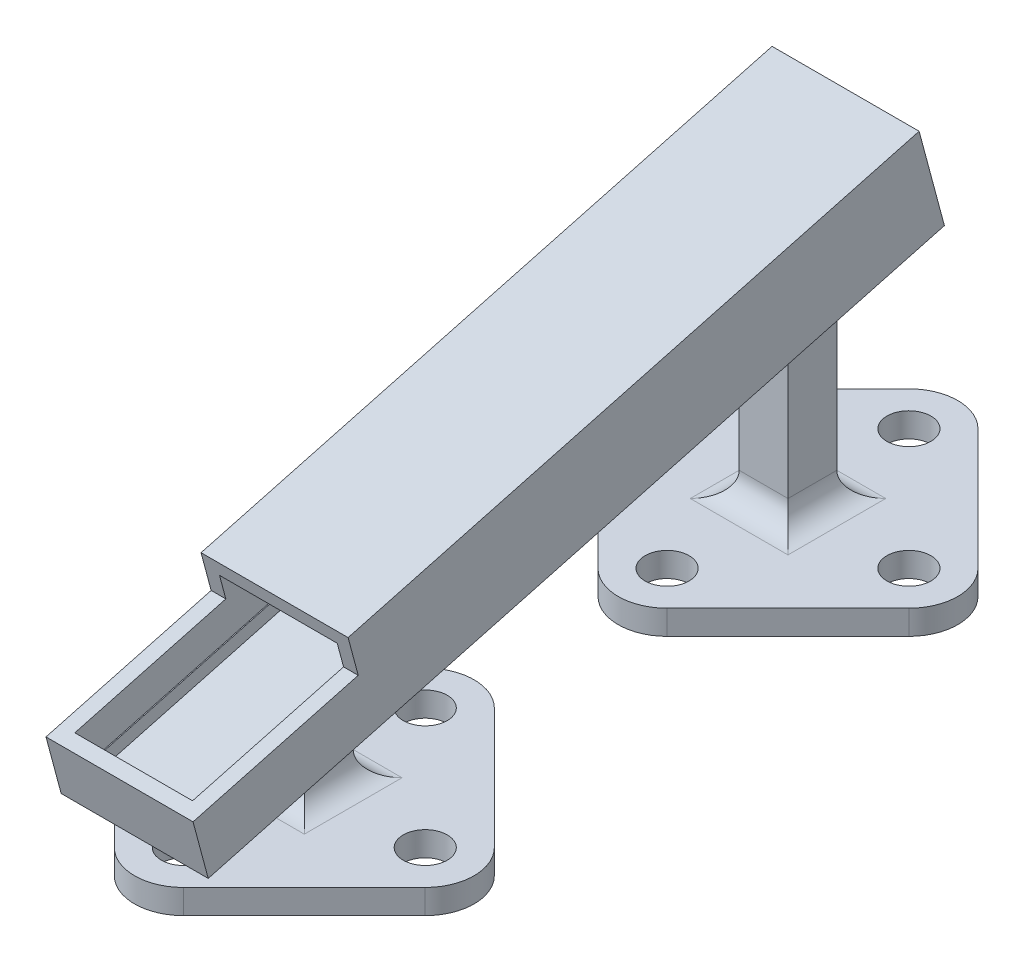
SolidWorks part; units mm, degrees
ref_plane "Front" through (0, 0, 0) normal (0, 0, 1) x (1, 0, 0)
ref_plane "Top" through (0, 0, 0) normal (0, 1, 0) x (1, 0, 0)
ref_plane "Right" through (0, 0, 0) normal (1, 0, 0) x (0, 0, -1)
ref_axis "Axis1" through (0, 55, 0) along (0, -1, 0)
ref_axis "Axis2" through (88.99, 0, 0) along (-1, 0, 0)
ref_axis "Axis3" through (0, 0, 55) along (0, 0, -1)
sketch "Sketch1" plane through (0, 0, 0) normal (0, 1, 0) x (1, 0, 0)
  line L0 (-24.75, 0) -> (0, 24.75) construction
  line L9 (-24.75, 0) -> (0, -24.75) construction
  line L11 (0, 24.75) -> (24.75, 0) construction
  line L12 (0, -24.75) -> (24.75, 0) construction
  line L13 (-24.75, 0) -> (24.75, 0) construction
  line L14 (0, 24.75) -> (0, -24.75) construction
  line L15 (-31.8211, 7.0711) -> (-7.0711, 31.8211)
  line L16 (7.0711, 31.8211) -> (31.8211, 7.0711)
  line L17 (7.0711, -31.8211) -> (31.8211, -7.0711)
  line L18 (-31.8211, -7.0711) -> (-7.0711, -31.8211)
  line L19 (0, -38.8921) -> (38.8921, 0) construction
  line L20 (-38.8921, 0) -> (0, -38.8921) construction
  line L21 (0, 38.8921) -> (38.8921, 0) construction
  line L22 (-38.8921, 0) -> (0, 38.8921) construction
  arc A4 (7.0711, -31.8211) -> (-7.0711, -31.8211) centre (0, -24.75) cw
  arc A5 (31.8211, 7.0711) -> (31.8211, -7.0711) centre (24.75, 0) cw
  arc A6 (-7.0711, 31.8211) -> (7.0711, 31.8211) centre (0, 24.75) cw
  arc A7 (-31.8211, 7.0711) -> (-31.8211, -7.0711) centre (-24.75, 0) ccw
  circle A8 centre (0, 24.75) radius 4.5
  circle A9 centre (24.75, 0) radius 4.5
  circle A10 centre (0, -24.75) radius 4.5
  circle A11 centre (-24.75, 0) radius 4.5
  point P1 (0, 0)
  dimension "D3" = 10
  dimension "D4" = 9
  dimension "D1" = 49.5
  dimension "D2" = 10
extrude "Boss-Extrude1" add sketch "Sketch1" along normal mid plane 5
ref_plane "Plane1" through (0, 0, 49.5) normal (0, 0, 1) x (1, 0, 0)
mirror "Mirror3" about plane through (0, 0, 49.5) normal (0, 0, 1) of bodies 101
sketch "Sketch2" plane through (0, 0, 0) normal (1, 0, 0) x (0, 0, -1)
  line L0 (-106.0711, 2.5) -> (-130.8211, 2.5) construction
  line L1 (-104, 2.5) -> (-94, 2.5)
  line L2 (-104, 2.5) -> (-104, 47.5)
  line L3 (-104, 47.5) -> (-94, 47.5)
  line L4 (-94, 2.5) -> (-94, 47.5)
  line L5 (-106.0711, -2.5) -> (-91.9289, -2.5) construction
  line L6 (-67.1789, -2.5) -> (-91.9289, -2.5) construction
  point P8 (-99, -2.5)
  point P9 (-99, 47.5)
  dimension "D1" = 10
  dimension "D2" = 50
extrude "Boss-Extrude2" add sketch "Sketch2" along normal mid plane 10 separate body
mirror "Mirror5" about plane through (0, 0, 49.5) normal (0, 0, 1) of bodies 103
sketch "Sketch3" plane through (0, 0, 0) normal (1, 0, 0) x (0, 0, -1)
  line L0 (-104, 17.5) -> (5, 46.7065)
  line L1 (-67.1789, -2.5) -> (-91.9289, -2.5) construction
  line L2 (-104, 47.5) -> (-104, 2.5) construction
  line L3 (-106.0711, 2.5) -> (-130.8211, 2.5) construction
  line L4 (5, 47.5) -> (5, 2.5) construction
  point P6 (-104, 17.5)
  dimension "D1" = 15
  dimension "D2" = 15
extrude "Cut-Extrude1" cut sketch "Sketch3" against normal through all both and the other way through all
sketch "Sketch4" plane through (0, 0, 0) normal (1, 0, 0) x (0, 0, -1)
  line L0 (-130.8211, 10.3133) -> (14.0678, 49.1362)
  line L1 (-130.8211, 10.3133) -> (-131.3387, 12.2452)
  line L2 (14.0678, 49.1362) -> (13.5502, 51.068)
  line L3 (-131.3387, 12.2452) -> (13.5502, 51.068)
  line L6 (-104, 17.5) -> (-94, 20.1795) construction
  dimension "D1" = 2
  dimension "D2" = 150
extrude "Boss-Extrude3" add sketch "Sketch4" along normal mid plane 24.1 separate body
combine bodies "Combine1" operation type add bodies to combine 102 106
combine bodies "Combine2" operation type add bodies to combine 107 101
fillet "Fillet1" radius 5 4 edges at (0, 2.5, 94) (-5, 2.5, 99) (0, 2.5, 104) (5, 2.5, 99)
fillet "Fillet2" radius 5 4 edges at (0, 2.5, 5) (0, 2.5, -5) (-5, 2.5, 0) (5, 2.5, 0)
sketch "Sketch5" plane through (0, 44.2596, 11.8593) normal (0, 0.9659, 0.2588) x (1, 0, 0)
  line L0 (12.05, -111.6442) -> (0, -111.6442) construction
  line L1 (12.05, 26.3058) -> (12.05, -123.6942) construction
  line L2 (0, -111.6442) -> (0, -123.6942) construction
  line L3 (12.05, -123.6942) -> (-12.05, -123.6942) construction
  line L4 (-11.83, -111.6442) -> (-12.05, -123.6942)
  line L5 (-12.05, -123.6942) -> (0, -123.6942)
  line L6 (0, -123.6942) -> (12.05, -123.6942)
  line L7 (12.05, -123.6942) -> (12.05, -111.6442)
  circle A0 centre (0, -111.6442) radius 8.73 construction
  circle A1 centre (0, -111.6442) radius 8.83
  circle A2 centre (0, -111.6442) radius 11.83
  dimension "D1" = 17.46
  dimension "D2" = 0.1
  dimension "D3" = 3
sketch "Sketch6" plane through (0, 44.2596, 11.8593) normal (0, 0.9659, 0.2588) x (1, 0, 0)
  line L4 (-12.05, 26.3058) -> (-12.05, -123.6942)
  line L5 (-12.05, -123.6942) -> (12.05, -123.6942)
  line L6 (12.05, -123.6942) -> (12.05, 26.3058)
  line L7 (12.05, 26.3058) -> (-12.05, 26.3058)
  line L8 (-12.05, 26.3058) -> (-12.05, -123.6942)
  line L9 (-12.05, -123.6942) -> (12.05, -123.6942)
  line L10 (12.05, -123.6942) -> (12.05, 26.3058)
  line L11 (12.05, 26.3058) -> (-12.05, 26.3058)
  line L16 (-15.05, 29.3058) -> (-15.05, -126.6942)
  line L17 (-15.05, -126.6942) -> (15.05, -126.6942)
  line L18 (15.05, -126.6942) -> (15.05, 29.3058)
  line L19 (15.05, 29.3058) -> (-15.05, 29.3058)
  line L20 (-15.05, 29.3058) -> (-15.05, -126.6942)
  line L21 (-15.05, -126.6942) -> (15.05, -126.6942)
  line L22 (15.05, -126.6942) -> (15.05, 29.3058)
  line L23 (15.05, 29.3058) -> (-15.05, 29.3058)
  dimension "D1" = 0
  dimension "D2" = 3
extrude "Boss-Extrude4" add sketch "Sketch6" against normal up to vertex (2 mm away) and the other way blind 10 up to point (12.05, 49.1362, -14.0678)
sketch "Sketch7" plane through (0, 53.9188, 14.4475) normal (0, 0.9659, 0.2588) x (1, 0, 0)
  line L0 (12.05, 26.3058) -> (12.05, -123.6942) construction
  line L1 (12.05, 26.3058) -> (12.05, -91.6942)
  line L3 (-12.05, 26.3058) -> (-12.05, -123.6942) construction
  line L4 (15.05, 29.3058) -> (-15.05, 29.3058)
  line L5 (-15.05, 29.3058) -> (-15.05, -126.6942)
  line L6 (-15.05, -126.6942) -> (15.05, -126.6942)
  line L7 (15.05, -126.6942) -> (15.05, 29.3058)
  line L8 (15.05, 29.3058) -> (-15.05, 29.3058)
  line L9 (-15.05, 29.3058) -> (-15.05, -91.6942)
  line L11 (15.05, -91.6942) -> (15.05, 29.3058)
  line L12 (12.05, 26.3058) -> (-12.05, 26.3058) construction
  line L14 (-12.05, 26.3058) -> (-12.05, -91.6942)
  line L15 (12.05, 26.3058) -> (-12.05, 26.3058)
  line L16 (15.05, -91.6942) -> (12.05, -91.6942)
  line L17 (-12.05, -91.6942) -> (-15.05, -91.6942)
  line L18 (-15.05, -126.6942) -> (15.05, -126.6942) construction
  dimension "D2" = 35
  dimension "D1" = 0
extrude "Boss-Extrude5" add sketch "Sketch7" along normal blind 5
sketch "Sketch8" plane through (0, 58.7485, 15.7416) normal (0, 0.9659, 0.2588) x (1, 0, 0)
  line L0 (-15.05, 29.3058) -> (-15.05, -91.6942) construction
  line L1 (-15.05, -91.6942) -> (15.05, -91.6942)
  line L2 (-15.05, -91.6942) -> (-15.05, 29.3058)
  line L3 (-15.05, 29.3058) -> (15.05, 29.3058)
  line L4 (15.05, -91.6942) -> (15.05, 29.3058)
  point P7 (-15.05, -90.9273)
extrude "Boss-Extrude6" add sketch "Sketch8" along normal blind 3
sketch "Sketch10" plane through (0, 6.8085, -25.4095) normal (0, -0.2588, 0.9659) x (1, 0, 0)
  line L4 (-12.05, 45.8209) -> (12.05, 45.8209)
  line L5 (12.05, 45.8209) -> (12.05, 60.8209)
  line L6 (12.05, 60.8209) -> (-12.05, 60.8209)
  line L7 (-12.05, 60.8209) -> (-12.05, 45.8209)
  line L8 (-12.05, 45.8209) -> (12.05, 45.8209)
  line L9 (12.05, 45.8209) -> (12.05, 60.8209)
  line L10 (12.05, 60.8209) -> (-12.05, 60.8209)
  line L11 (-12.05, 60.8209) -> (-12.05, 45.8209)
  dimension "D1" = 0
extrude "Cut-Extrude2" cut sketch "Sketch10" against normal up to next
sketch "Sketch11" plane through (0, 7.5849, -28.3073) normal (0, 0.2588, -0.9659) x (-1, 0, 0)
  line L0 (-12.05, 45.8209) -> (-11.85, 45.8209)
  line L1 (-12.05, 45.8209) -> (12.05, 45.8209) construction
  line L2 (-11.85, 45.8209) -> (-11.85, 48.5209)
  line L3 (-11.85, 48.5209) -> (-12.05, 48.5209)
  line L4 (-12.05, 60.8209) -> (-12.05, 45.8209) construction
  line L5 (-12.05, 48.5209) -> (-12.05, 45.8209)
  line L6 (0, 43.8209) -> (0, 45.8209) construction
  line L7 (-15.05, 43.8209) -> (15.05, 43.8209) construction
  line L8 (12.05, 48.5209) -> (12.05, 45.8209)
  line L9 (11.85, 48.5209) -> (12.05, 48.5209)
  line L10 (11.85, 45.8209) -> (11.85, 48.5209)
  line L11 (12.05, 45.8209) -> (11.85, 45.8209)
  dimension "D1" = 0.2
  dimension "D2" = 2.7
extrude "Boss-Extrude7" add sketch "Sketch11" against normal up to surface (153 mm away) up to face at (0, 17.0748, 132.6328)
